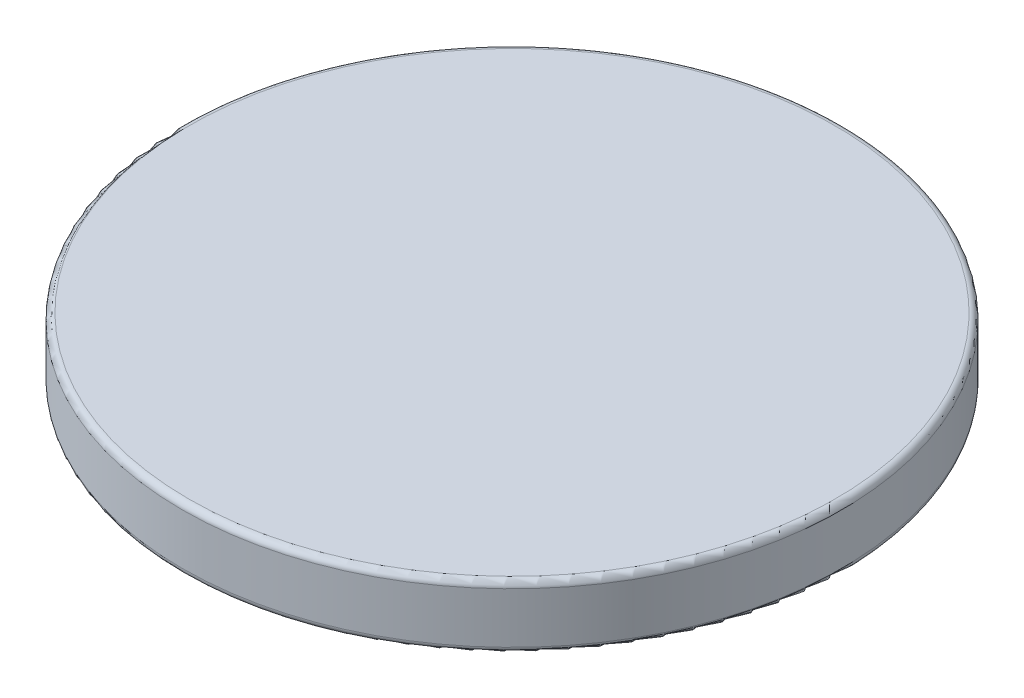
SolidWorks part; units mm, degrees
ref_plane "Front" through (0, 0, 0) normal (0, 0, 1) x (1, 0, 0)
ref_plane "Top" through (0, 0, 0) normal (0, 1, 0) x (1, 0, 0)
ref_plane "Right" through (0, 0, 0) normal (1, 0, 0) x (0, 0, -1)
sketch "Sketch2" plane through (0, 0, 0) normal (0, 1, 0) x (1, 0, 0)
  circle A0 centre (0, 0) radius 66.04
  dimension "D1" = 132.08
extrude "Boss-Extrude1" add sketch "Sketch2" against normal blind 12.7
fillet "Fillet1" radius 1.27 2 edges at (0, -12.7, 66.04) (0, 0, 66.04)
